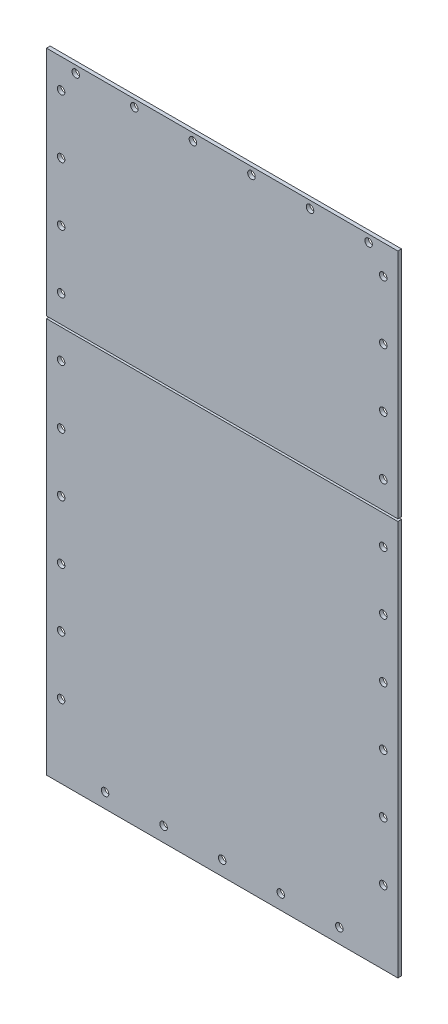
SolidWorks part; units mm, degrees
material "Copper"
ref_plane "Front Plane" through (0, 0, 0) normal (0, 0, 1) x (1, 0, 0)
ref_plane "Top Plane" through (0, 0, 0) normal (0, 1, 0) x (1, 0, 0)
ref_plane "Right Plane" through (0, 0, 0) normal (1, 0, 0) x (0, 0, -1)
sketch "Sketch1" plane through (0, 0, 0) normal (0, 0, 1) x (1, 0, 0)
  line L0 (0, -100.6) -> (152.4, -100.6)
  line L1 (0, 0) -> (152.4, 0)
  line L2 (0, 0) -> (0, -273.05)
  line L3 (0, -273.05) -> (152.4, -273.05)
  line L4 (152.4, 0) -> (152.4, -273.05)
  line L5 (0, -101.6) -> (152.4, -101.6)
  circle A0 centre (6.35, -12.7) radius 1.632
  circle A1 centre (146.05, -12.7) radius 1.632
  circle A2 centre (146.05, -38.1) radius 1.632
  circle A3 centre (146.05, -63.5) radius 1.632
  circle A4 centre (146.05, -88.9) radius 1.632
  circle A5 centre (146.05, -114.3) radius 1.632
  circle A6 centre (146.05, -139.7) radius 1.632
  circle A7 centre (146.05, -165.1) radius 1.632
  circle A8 centre (146.05, -190.5) radius 1.632
  circle A9 centre (146.05, -215.9) radius 1.632
  circle A10 centre (146.05, -241.3) radius 1.632
  circle A11 centre (6.35, -38.1) radius 1.6319
  circle A12 centre (6.35, -63.5) radius 1.6319
  circle A13 centre (6.35, -88.9) radius 1.6319
  circle A14 centre (6.35, -114.3) radius 1.6319
  circle A15 centre (6.35, -139.7) radius 1.6319
  circle A16 centre (6.35, -165.1) radius 1.632
  circle A17 centre (6.35, -190.5) radius 1.632
  circle A18 centre (6.35, -215.9) radius 1.632
  circle A19 centre (6.35, -241.3) radius 1.632
  circle A20 centre (12.7, -3.175) radius 1.632
  circle A21 centre (38.1, -3.175) radius 1.632
  circle A22 centre (63.5, -3.175) radius 1.632
  circle A23 centre (88.9, -3.175) radius 1.632
  circle A24 centre (114.3, -3.175) radius 1.632
  circle A25 centre (139.7, -3.175) radius 1.632
  circle A26 centre (25.4, -266.7) radius 1.632
  circle A27 centre (50.8, -266.7) radius 1.632
  circle A28 centre (76.2, -266.7) radius 1.632
  circle A29 centre (101.6, -266.7) radius 1.632
  circle A30 centre (127, -266.7) radius 1.632
  dimension "D3" = 3.2639
  dimension "D1" = 273.05
  dimension "D2" = 152.4
  dimension "D4" = 12.7
  dimension "D5" = 6.35
  dimension "D8" = 6.35
  dimension "D9" = 25.4
  dimension "D10" = 3.175
  dimension "D11" = 12.7
  dimension "D13" = 25.4
  dimension "D14" = 6.35
  dimension "D15" = 25.4
  dimension "D17" = 25.4
  dimension "D18" = 11.7
  dimension "D19" = 1
  dimension "D6" = 2
  dimension "D7" = 10
  dimension "D12" = 6
  dimension "D16" = 5
extrude "Boss-Extrude1" add sketch "Sketch1" along normal blind 1.5875 contours L4 L1 L2 L0 A25 A24 A23 A22 A21 A20 A13 A12 A11 A4 A3 A2 A1 A0 | L5 L2 L3 L4 A30 A29 A28 A27 A26 A19 A18 A17 A16 A15 A14 A10 A9 A8 A7 A6 A5 region at (76.2, -50.4533, 0) region at (76.2, -187.234, 0)
equation "\"D18@Sketch1\"=(\"D9@Sketch1\"/2)-1"
